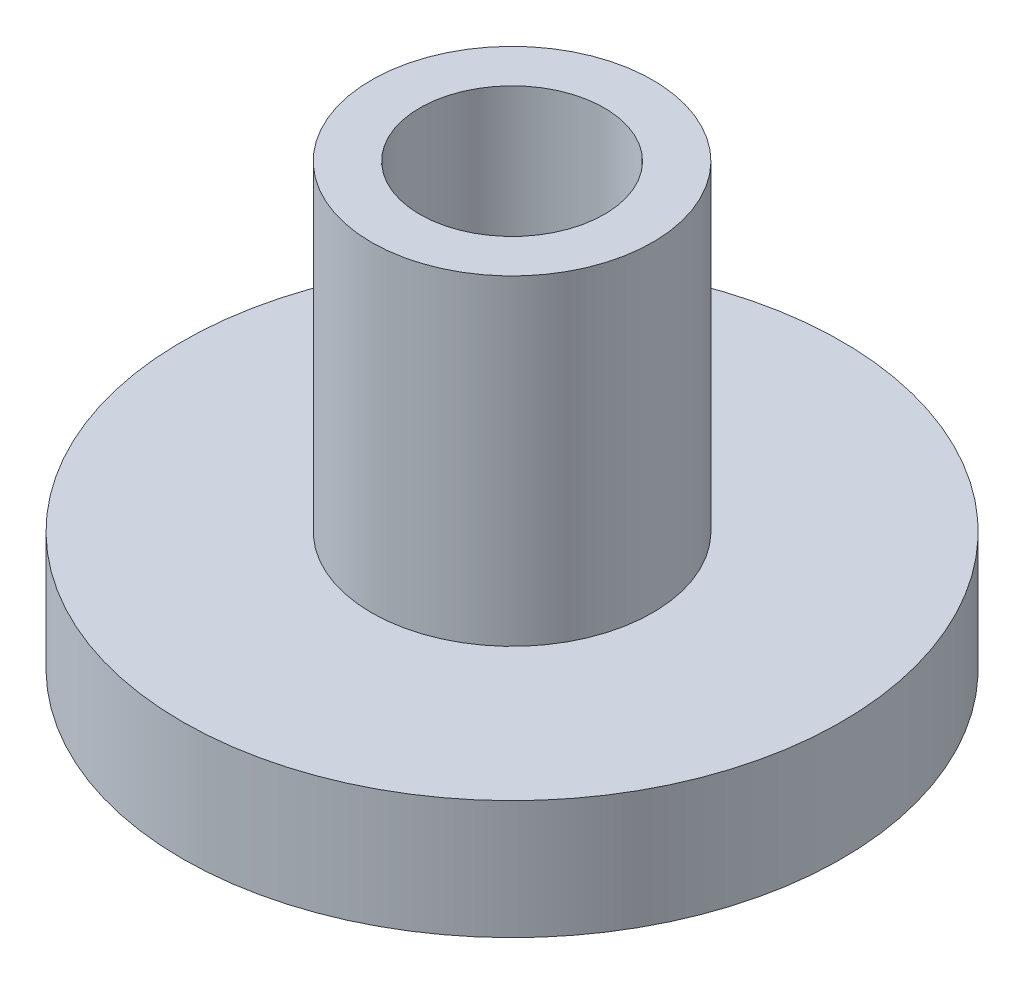
SolidWorks part; units mm, degrees
ref_plane "Front Plane" through (0, 0, 0) normal (0, 0, 1) x (1, 0, 0)
ref_plane "Top Plane" through (0, 0, 0) normal (0, 1, 0) x (1, 0, 0)
ref_plane "Right Plane" through (0, 0, 0) normal (1, 0, 0) x (0, 0, -1)
sketch "Sketch1" plane through (0, 0, 0) normal (0, 1, 0) x (1, 0, 0)
  circle A0 centre (0, 0) radius 7.5
  dimension "D1" = 15
extrude "base_body" add sketch "Sketch1" along normal blind 10
sketch "Sketch2" plane through (0, 10, 0) normal (0, 1, 0) x (1, 0, 0)
  circle A0 centre (0, 0) radius 2.1
  dimension "D1" = 4.2
extrude "shaft_bearing_cut" cut sketch "Sketch2" against normal through all
sketch "Sketch3" plane through (0, 10, 0) normal (0, 1, 0) x (1, 0, 0)
  circle A0 centre (0, 0) radius 3.2
  dimension "D1" = 6.4
extrude "lathe_cut" cut sketch "Sketch3" against normal blind 7.3 flip side to cut
